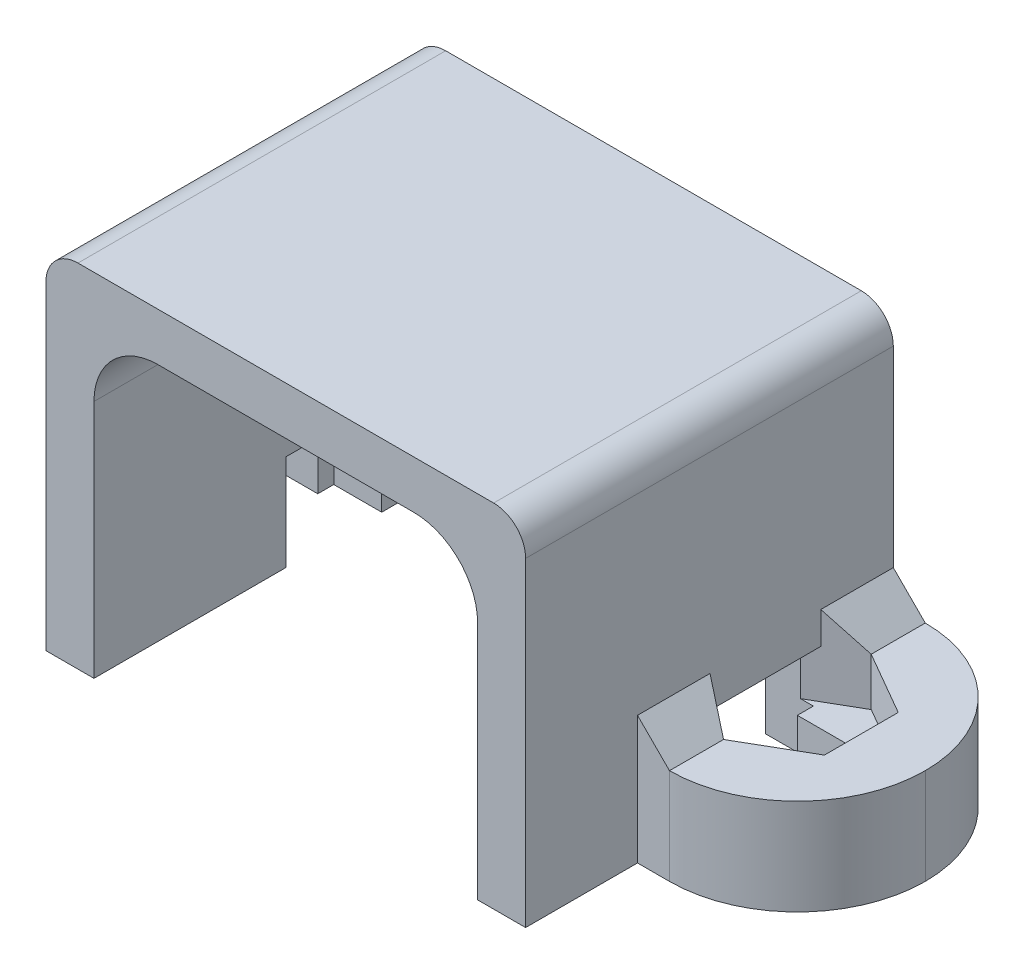
SolidWorks part; units mm, degrees
ref_plane "前视基准面" through (0, 0, 0) normal (0, 0, 1) x (1, 0, 0)
ref_plane "上视基准面" through (0, 0, 0) normal (0, 1, 0) x (1, 0, 0)
ref_plane "右视基准面" through (0, 0, 0) normal (1, 0, 0) x (0, 0, -1)
other "Configuration Table"
sketch "草图1" plane through (0, 0, 0) normal (0, 0, 1) x (1, 0, 0)
  line L0 (0, 0) -> (0, 11) construction
  line L1 (-7.5, 11) -> (7.5, 11)
  line L2 (-7.5, 11) -> (-7.5, 0)
  line L3 (-7.5, 0) -> (7.5, 0)
  line L4 (7.5, 11) -> (7.5, 0)
  dimension "D1" = 15
  dimension "D2" = 11
extrude "凸台-拉伸1" add sketch "草图1" along normal blind 11.5
sketch "草图2" plane through (0, 0, 0) normal (0, -1, 0) x (1, 0, 0)
  line L0 (0, 0) -> (0, 11.5) construction
  line L1 (-7.5, 11.5) -> (7.5, 11.5) construction
  line L2 (-7.5, 0) -> (-12.5, 0)
  line L3 (7.5, 8) -> (12.5, 8)
  line L4 (7.5, 8) -> (7.5, 0)
  line L5 (7.5, 0) -> (12.5, 0)
  line L6 (12.5, 8) -> (12.5, 0)
  line L7 (-12.5, 8) -> (-12.5, 0)
  line L8 (-7.5, 8) -> (-12.5, 8)
  line L9 (-7.5, 8) -> (-7.5, 0)
  point P9 (7.5, 0)
  dimension "D1" = 5
  dimension "D2" = 8
extrude "凸台-拉伸2" add sketch "草图2" against normal blind 3
sketch "草图3" plane through (0, 0, 0) normal (0, 0, -1) x (-1, 0, 0)
  line L1 (-6, 9.5) -> (6, 9.5)
  line L2 (-6, 9.5) -> (-6, 0)
  line L3 (-6, 0) -> (6, 0)
  line L4 (6, 9.5) -> (6, 0)
  point P4 (0, 0)
  dimension "D1" = 12
  dimension "D2" = 9.5
extrude "切除-拉伸1" cut sketch "草图3" against normal through all
sketch "草图4" plane through (0, 3, 0) normal (0, 1, 0) x (1, 0, 0)
  line L0 (0, -11.5) -> (0, 0) construction
  line L1 (7.5, -11.5) -> (-7.5, -11.5) construction
  line L2 (7.5, -8) -> (7.5, 0) construction
  line L3 (8.5, -1.6906) -> (6.5, -2.8453)
  line L4 (6.5, -2.8453) -> (6.5, -5.1547)
  line L5 (6.5, -5.1547) -> (8.5, -6.3094)
  line L6 (8.5, -6.3094) -> (10.5, -5.1547)
  line L7 (10.5, -5.1547) -> (10.5, -2.8453)
  line L8 (10.5, -2.8453) -> (8.5, -1.6906)
  line L9 (7.5, 0) -> (12.5, 0) construction
  line L10 (-10.5, -2.8453) -> (-8.5, -1.6906)
  line L11 (-10.5, -5.1547) -> (-10.5, -2.8453)
  line L12 (-8.5, -6.3094) -> (-10.5, -5.1547)
  line L13 (-6.5, -5.1547) -> (-8.5, -6.3094)
  line L14 (-6.5, -2.8453) -> (-6.5, -5.1547)
  line L15 (-8.5, -1.6906) -> (-6.5, -2.8453)
  circle A0 centre (8.5, -4) radius 2 construction
  point P6 (8.3639, -1.5627)
  point P14 (8.7568, -3.6484)
  point P15 (1.6231, 10.1958)
  dimension "D1" = 4
  dimension "D2" = 1
  dimension "D3" = 4
extrude "切除-拉伸2" cut sketch "草图4" against normal blind 1.5
sketch "草图5" plane through (0, 0, 0) normal (0, -1, 0) x (1, 0, 0)
  line L0 (0, 0) -> (0, 11.5) construction
  line L1 (-6, 11.5) -> (6, 11.5) construction
  line L2 (6, 11.5) -> (6, 0) construction
  line L3 (6, 5.5) -> (7.5, 5.5)
  line L4 (6, 5.5) -> (6, 2.5)
  line L5 (6, 2.5) -> (7.5, 2.5)
  line L6 (7.5, 5.5) -> (7.5, 2.5)
  line L7 (-6, 0) -> (6, 0) construction
  line L8 (-6, 2.5) -> (-7.5, 2.5)
  line L9 (-7.5, 5.5) -> (-7.5, 2.5)
  line L10 (-6, 5.5) -> (-7.5, 5.5)
  line L11 (-6, 5.5) -> (-6, 2.5)
  point P9 (1.8048, -10.2807)
  point P10 (6, 1.5118)
  point P13 (6, 4)
  dimension "D1" = 1.5
  dimension "D2" = 3
  dimension "D3" = 4
extrude "切除-拉伸3" cut sketch "草图5" against normal blind 3
sketch "草图6" plane through (0, 0, 0) normal (0, -1, 0) x (1, 0, 0)
  line L0 (0, 0) -> (0, 11.5) construction
  line L1 (7.5, 5) -> (10, 5)
  line L2 (7.5, 5) -> (7.5, 3)
  line L3 (7.5, 3) -> (10, 3)
  line L4 (10, 5) -> (10, 3)
  line L5 (-6, 11.5) -> (6, 11.5) construction
  line L6 (7.5, 2.5) -> (7.5, 5.5) construction
  line L7 (-7.5, 3) -> (-10, 3)
  line L8 (-10, 5) -> (-10, 3)
  line L9 (-7.5, 5) -> (-10, 5)
  line L10 (-7.5, 5) -> (-7.5, 3)
  point P9 (7.5, 3.0565)
  point P12 (7.5, 4)
  point P13 (7.5, 4)
  dimension "D1" = 2
  dimension "D2" = 2.5
extrude "切除-拉伸4" cut sketch "草图6" against normal blind 1.5
fillet "圆角1" radius 2 2 edges at (6, 9.5, 5.75) (-6, 9.5, 5.75)
fillet "圆角2" radius 4 4 edges at (12.5, 1.5, 0) (12.5, 1.5, 8) (-12.5, 1.5, 0) (-12.5, 1.5, 8)
fillet "圆角3" radius 1 4 edges at (10, 0.75, 5) (10, 0.75, 3) (-10, 0.75, 3) (-10, 0.75, 5)
chamfer "倒角1" distance 1 angle 45 4 edges at (7.5, 3, 1.134) (7.5, 3, 6.866) (-7.5, 3, 6.866) (-7.5, 3, 1.134)
fillet "圆角4" radius 1 2 edges at (-7.5, 11, 5.75) (7.5, 11, 5.75)
